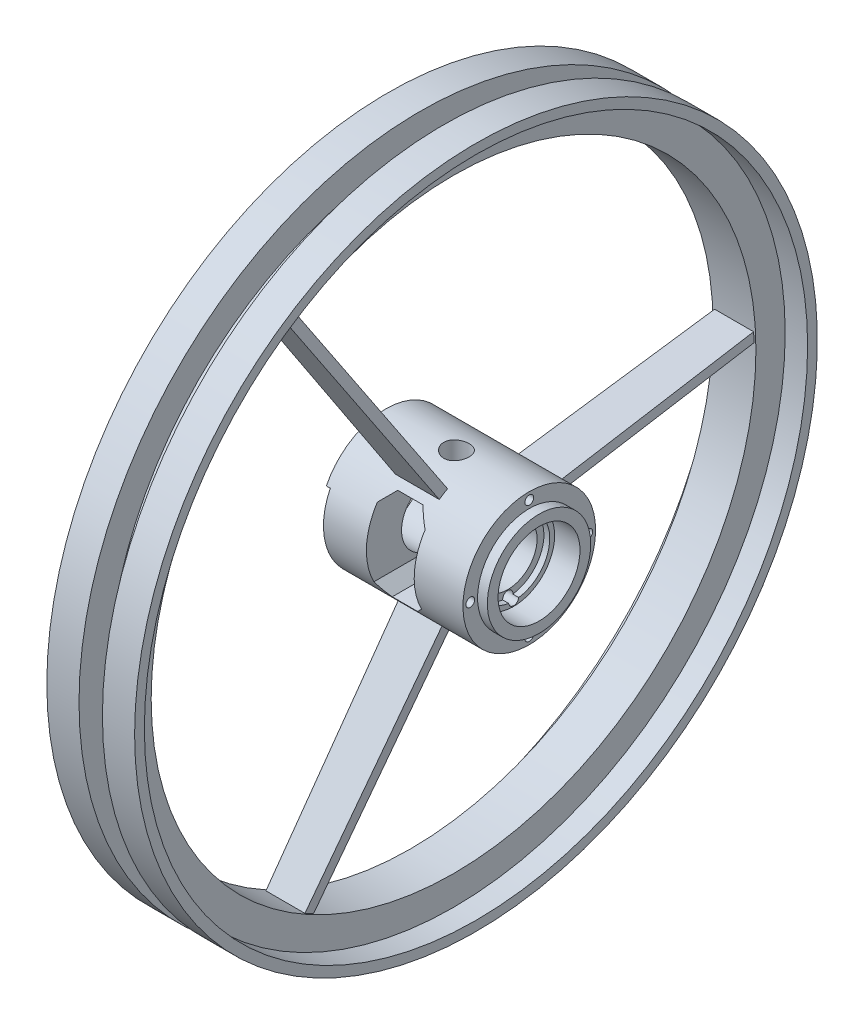
SolidWorks part; units mm, degrees
ref_plane "Front Plane" through (0, 0, 0) normal (0, 0, 1) x (1, 0, 0)
ref_plane "Top Plane" through (0, 0, 0) normal (0, 1, 0) x (1, 0, 0)
ref_plane "Right Plane" through (0, 0, 0) normal (1, 0, 0) x (0, 0, -1)
sketch "Sketch17" plane through (0, 0, 0) normal (0, 0, 1) x (1, 0, 0)
  line L0 (0, 0) -> (156.5215, 0) construction
sketch "Sketch1" plane through (0, 0, 0) normal (1, 0, 0) x (0, 0, -1)
  circle A0 centre (0, 0) radius 68
extrude "Boss-Extrude1" add sketch "Sketch1" along normal blind 157 contours A0
sketch "Sketch2" plane through (0, 0, 0) normal (-1, 0, 0) x (0, 0, 1)
  circle A0 centre (0, 0) radius 26
extrude "Cut-Extrude1" cut sketch "Sketch2" against normal up to next
sketch "Sketch3" plane through (0, 0, 0) normal (-1, 0, 0) x (0, 0, 1)
  line L1 (-68, 30) -> (68, 30)
  line L2 (-68, 30) -> (-68, -68)
  line L3 (-68, -68) -> (68, -68)
  line L4 (68, 30) -> (68, -68)
  circle A2 centre (0, 0) radius 68 construction
  circle A3 centre (0, 0) radius 26 construction
  dimension "D1" = 30
  dimension "D2" = 68
  dimension "D3" = 42
  dimension "D4" = 68
  dimension "D5" = 68
extrude "Cut-Extrude2" cut sketch "Sketch3" against normal blind 4 contours L2 L3 L4 L1
sketch "Sketch4" plane through (4, 0, 0) normal (-1, 0, 0) x (0, 0, 1)
  line L3 (-13.5, 29) -> (13.5, 29)
  arc A2 (13.5, 29) -> (-13.5, 29) centre (0, 0) cw
  dimension "D1" = 27
  dimension "D2" = 29
extrude "Cut-Extrude3" cut sketch "Sketch4" against normal blind 44
sketch "Sketch7" plane through (157, 0, 0) normal (1, 0, 0) x (0, 0, -1)
  circle A0 centre (0, 0) radius 42
extrude "Cut-Extrude4" cut sketch "Sketch7" against normal blind 26
sketch "Sketch8" plane through (131, 0, 0) normal (1, 0, 0) x (0, 0, -1)
  circle A0 centre (0, 0) radius 37
extrude "Cut-Extrude5" cut sketch "Sketch8" against normal blind 6 contours A0
sketch "Sketch9" plane through (125, 0, 0) normal (1, 0, 0) x (0, 0, -1)
  circle A0 centre (0, 0) radius 30
extrude "Cut-Extrude6" cut sketch "Sketch9" against normal blind 30 contours A0
ref_plane "Plane2" through (0, 0, 68) normal (0, 0, 1) x (1, 0, 0)
sketch "Sketch12" plane through (0, 0, 68) normal (0, 0, 1) x (1, 0, 0)
  line L0 (48, 37.576) -> (48, -31.4216)
  line L1 (48, -31.4216) -> (59.3739, -42.7955)
  line L2 (59.3739, -42.7955) -> (85.3739, -42.7955)
  line L3 (85.3739, -42.7955) -> (97, -31.1695)
  line L4 (97, -31.1695) -> (97, 37.3239)
  line L5 (97, 37.3239) -> (85.3739, 48.9499)
  line L6 (85.3739, 48.9499) -> (59.3739, 48.9499)
  line L7 (59.3739, 48.9499) -> (48, 37.576)
  line L8 (157, -68) -> (157, 68) construction
  line L9 (4, 30) -> (4, -68) construction
  dimension "D1" = 60
  dimension "D2" = 44
  dimension "D3" = 26
  dimension "D4" = 26
  dimension "D5" = 135
  dimension "D6" = 135
  dimension "D7" = 135
  dimension "D8" = 135
extrude "Cut-Extrude8" cut sketch "Sketch12" against normal blind 71 contours L0 L1 L2 L3 L4 L5 L6 L7
sketch "Sketch16" plane through (0, 0, 0) normal (-1, 0, 0) x (0, 0, 1)
  line L0 (35.9404, 57.726) -> (61.0246, 30) construction
  line L1 (35.9404, 57.726) -> (0, 68) construction
  arc A0 (61.0246, 30) -> (-61.0246, 30) centre (0, 0) ccw construction
  dimension "D1" = 37.38
  dimension "D2" = 37.3892
ref_plane "Plane5" through (0, 68, 0) normal (0, 1, 0) x (1, 0, 0)
sketch "Sketch23" plane through (0, 68, 0) normal (0, 1, 0) x (1, 0, 0)
  point P9 (72.3739, 0)
  dimension "D1" = 13
hole_wizard "Tap Drill for M1.2x0.25 Tap1" positions "Sketch23" profile "Sketch26" hole size "M1.2x0.25" standard "ISO"
sketch "Sketch26" plane through (72.3739, 68, 0) normal (1, 0, 0) x (0, 0, 1)
  line L0 (0, 0) -> (0, 68)
  line L1 (0, 68) -> (13, 68)
  line L2 (13, 68) -> (13, 0)
  line L5 (13, 0) -> (0, 0)
  line L10 (0, 68) -> (-13, 68) construction
  line L11 (0, -6.35) -> (0, 107.95) construction
  dimension "Hole Dia." = 26
  dimension "Hole Depth" = 68
  dimension "Drill Angle" = 180
sketch "Sketch27" plane through (157, 0, 0) normal (1, 0, 0) x (0, 0, -1)
  circle A0 centre (0, 0) radius 68
  circle A1 centre (0, 0) radius 53
  dimension "D1" = 136
  dimension "D2" = 106
extrude "Cut-Extrude9" cut sketch "Sketch27" against normal blind 10
sketch "Sketch29" plane through (147, 0, 0) normal (1, 0, 0) x (0, 0, -1)
  line L0 (0, 68) -> (0, 53) construction
  line L1 (53, 0) -> (68, 0) construction
  line L2 (0, -53) -> (0, -68) construction
  line L3 (-53, 0) -> (-68, 0) construction
  line L4 (-68, 86.35) -> (-68, -86.35) construction
  circle A0 centre (0, 0) radius 53 construction
  circle A1 centre (0, 0) radius 53 construction
  circle A2 centre (0, 0) radius 68 construction
  point P21 (0, 60.5)
  point P23 (60.5, 0)
  point P25 (0, -60.5)
  point P27 (-60.5, 0)
hole_wizard "M8 Clearance Hole1" positions "Sketch29" profile "Sketch30" hole size "M8" standard "ISO"
sketch "Sketch30" plane through (147, 0, 60.5) normal (0, 1, 0) x (0, 0, -1)
  line L0 (0, 0) -> (0, 37.7039)
  line L1 (0, 37.7039) -> (4.5, 35)
  line L2 (4.5, 35) -> (4.5, 0)
  line L5 (4.5, 0) -> (0, 0)
  line L10 (0, 37.7039) -> (-4.5, 35) construction
  line L11 (0, -6.35) -> (0, 107.95) construction
  dimension "Hole Dia." = 9
  dimension "Hole Depth" = 35
  dimension "Drill Angle" = 118
ref_plane "Plane4" through (0, 0, 0) normal (0, 0.5285, -0.8489) x (-1, 0, 0)
sketch "Sketch19" plane through (0, 0, 0) normal (0, 0.5285, -0.8489) x (-1, 0, 0)
  line L3 (-27.3689, 310) -> (-67.3689, 310)
  line L7 (-97, 30.0991) -> (-97, 61.7272) construction
  line L8 (-48, 30.3131) -> (-48, 61.8533) construction
  line L9 (0, 0) -> (-156.5215, 0) construction
  line L10 (-67.3689, 310) -> (-95, 66.5)
  line L11 (-95, 66.5) -> (-50, 66.5)
  line L12 (-50, 66.5) -> (-27.3689, 310)
  line L13 (0, 68) -> (-147, 68) construction
  point P4 (-67.3689, 310)
  dimension "D2" = 49
  dimension "D1" = 310
  dimension "D3" = 45
  dimension "D4" = 1.5
  dimension "D5" = 2
  dimension "D6" = 40
sketch "Sketch21" plane through (0, 0, 0) normal (0, 0.5285, -0.8489) x (-1, 0, 0)
  line L0 (-67.3689, 310) -> (-69.3689, 310)
  line L1 (-69.3689, 310) -> (-69.3689, 340)
  line L2 (-69.3689, 340) -> (-92.3689, 340)
  line L3 (-92.3689, 340) -> (-92.3689, 350)
  line L4 (-92.3689, 350) -> (-59.3689, 350)
  line L5 (-2.3689, 350) -> (-2.3689, 340)
  line L6 (-2.3689, 340) -> (-25.3689, 340)
  line L7 (-25.3689, 340) -> (-25.3689, 310)
  line L8 (-25.3689, 310) -> (-27.3689, 310)
  line L11 (-59.3689, 350) -> (-59.3689, 320)
  line L12 (-59.3689, 320) -> (-35.3689, 320)
  line L13 (-35.3689, 320) -> (-35.3689, 350)
  line L14 (-35.3689, 350) -> (-2.3689, 350)
  line L15 (-27.3689, 310) -> (-67.3689, 310) construction
  line L17 (-67.3689, 310) -> (-27.3689, 310)
  point P18 (-35.8149, 320)
  point P19 (-26.5195, 310)
  point P20 (-2.5195, 310)
  point P21 (-8.4134, 310)
  point P22 (-26.5195, 310)
  point P23 (-71.5195, 310)
  point P24 (-26.5195, 310)
  dimension "D5" = 2
  dimension "D2" = 10
  dimension "D3" = 10
  dimension "D7" = 10
  dimension "D8" = 90
  dimension "D11" = 40
  dimension "D12" = 40
  dimension "D10" = 2
  dimension "D6" = 10
  dimension "D9" = 10
  dimension "D4" = 23
  dimension "D13" = 24
revolve "Revolve1" add sketch "Sketch21" angle 360 about L0
extrude "Boss-Extrude4" add sketch "Sketch19" along normal mid plane 10
pattern_circular "CirPattern4" count 3 over 360 about axis through (0, 0, 0) along (1, 0, 0) of "Boss-Extrude4"
sketch "Esquisse4" plane through (131, 0, 0) normal (1, 0, 0) x (0, 0, -1)
  line L0 (0, 0) -> (0, -36) construction
  point P11 (0, -36)
  dimension "D1" = 36
  dimension "D2" = 0
hole_wizard "M10 Clearance Hole1" positions "Esquisse4" profile "Esquisse6" hole size "M10" standard "ANSI Metric"
sketch "Esquisse6" plane through (131, -36, 0) normal (0, 1, 0) x (0, 0, -1)
  line L0 (0, 0) -> (0, 15)
  line L1 (0, 15) -> (5.25, 15)
  line L2 (5.25, 15) -> (5.25, 0)
  line L5 (5.25, 0) -> (0, 0)
  line L10 (0, 15) -> (-5.25, 15) construction
  line L11 (0, -6.35) -> (0, 107.95) construction
  dimension "Hole Dia." = 10.5
  dimension "Hole Depth" = 15
  dimension "Drill Angle" = 180
equation "\"D1@Sketch3\"=26+8/2"
equation "\"D2@Sketch3\"=26+\"D3@Sketch3\""
equation "\"D4@Sketch3\"=\"D2@Sketch3\""
equation "\"D5@Sketch3\"=\"D2@Sketch3\""
equation "\"D5@Sketch19\"=(\"D2@Sketch19\"-\"D3@Sketch19\")/2"
equation "\"D12@Sketch21\"=\"D11@Sketch21\""
equation "\"D2@Sketch27\"=\"D1@Sketch27\"-15*2"
equation "\"D4@Sketch21\"=(\"D8@Sketch21\"-\"D6@Sketch21\"-\"D13@Sketch21\"-\"D9@Sketch21\")/2"
